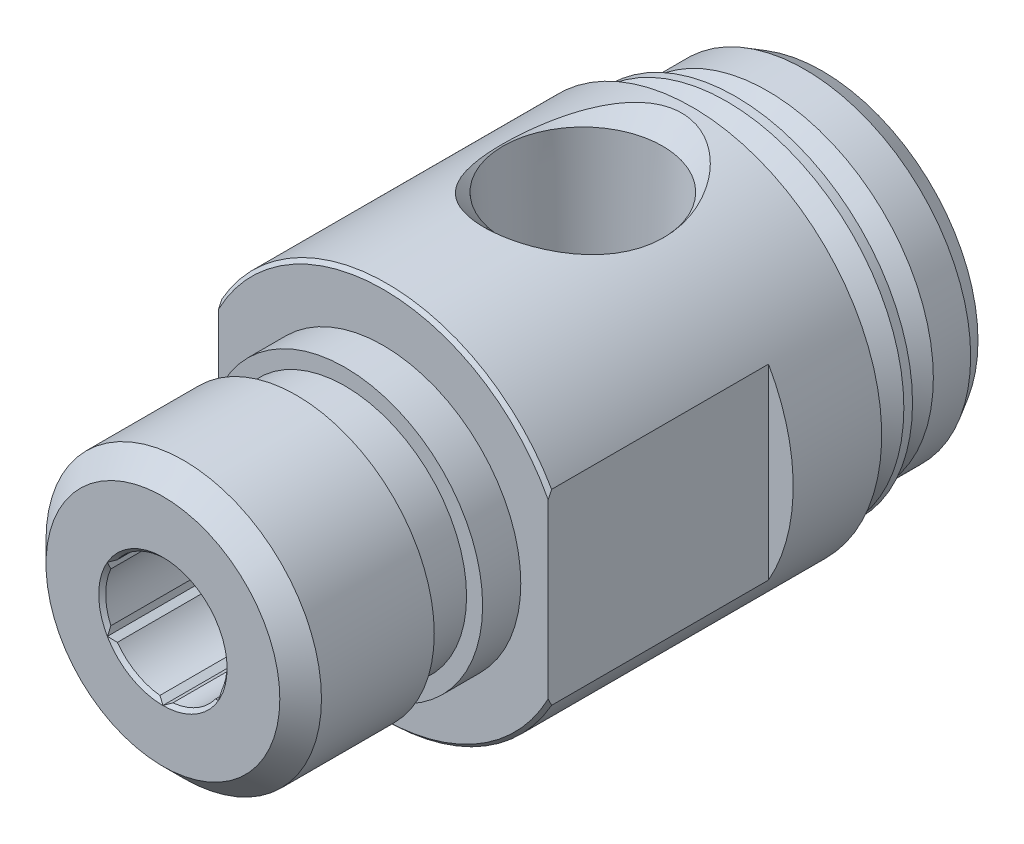
SolidWorks part; units mm, degrees
note: '?' marks a value the reader was unsure of.
ref_plane "Plane1" through (0, 0, 0) normal (0, 0, 1) x (1, 0, 0)
ref_plane "Plane2" through (0, 0, 0) normal (0, 1, 0) x (1, 0, 0)
ref_plane "Plane3" through (0, 0, 0) normal (1, 0, 0) x (0, 0, -1)
sketch "Sketch1" plane through (0, 0, 0) normal (0, 0, 1) x (1, 0, 0)
  circle A0 centre (0, 0) radius 9.55
  dimension "D1" = 19.1
extrude "TubeInterface1" add sketch "Sketch1" along normal blind 5
sketch "Sketch3" plane through (0, 0, 5) normal (0, 0, 1) x (1, 0, 0)
  circle A0 centre (0, 0) radius 10.922
  dimension "D1" = 21.844
extrude "Body" add sketch "Sketch3" along normal blind 20.3
chamfer "BodyChamfer" distance 0.2 angle 45 1 edges at (10.922, 0, 25.3)
sketch "Sketch4" plane through (0, 0, 25.3) normal (0, 0, 1) x (1, 0, 0)
  line L0 (0, 0) -> (0, 17.3061) construction
  line L1 (-9.5, 37.5) -> (-9.5, -37.5)
  line L2 (0, 0) -> (26.7246, 0) construction
  line L3 (9.5, 37.5) -> (9.5, -37.5)
  line L4 (9.5, 37.5) -> (19.5, 37.5)
  line L5 (19.5, 37.5) -> (19.5, -37.5)
  line L6 (-9.5, 37.5) -> (-19.5, 37.5)
  line L7 (-19.5, 37.5) -> (-19.5, -37.5)
  line L8 (-9.5, -37.5) -> (-19.5, -37.5)
  line L9 (9.5, -37.5) -> (19.5, -37.5)
  dimension "D1" = 19
  dimension "D2" = 10
  dimension "D3" = 75
extrude "Flats" cut sketch "Sketch4" against normal blind 12.7
sketch "Sketch5" plane through (0, 0, 25.3) normal (0, 0, 1) x (1, 0, 0)
  circle A0 centre (0, 0) radius 7.9375
  dimension "NN" = 15.875
extrude "MountThread1" add sketch "Sketch5" along normal blind 12.7
chamfer "MountThreadChamfer" distance 1.2 angle 45 1 edges at (7.9375, 0, 38)
sketch "Sketch17" plane through (0, 0, 0) normal (1, 0, 0) x (0, 0, -1)
  line L0 (-27.5, 17.727) -> (-27.5, -12.2127) construction
  line L1 (-25.3, -4.971) -> (-25.3, -10.722) construction
  line L2 (0, 0) -> (-12.6638, 0) construction
  line L3 (-25.1, 0) -> (-25.3, 0) construction
  line L6 (-30.3, 12) -> (-27.5, 12)
  line L7 (-30.3, 12) -> (-30.3, 7)
  line L8 (-30.3, 7) -> (-27.5, 7)
  line L9 (-27.5, 12) -> (-27.5, 7)
  dimension "D1" = 2.8
  dimension "D2" = 2.2
  dimension "D3" = 7
  dimension "D4" = 5
revolve "Cut-Revolve1" cut sketch "Sketch17" angle 360 about L2
sketch "Sketch8" plane through (0, 0, 0) normal (0, 0, 1) x (1, 0, 0)
  circle A0 centre (0, 0) radius 3.5
  dimension "D1" = 7
extrude "ThruBore" cut sketch "Sketch8" along normal through all
sketch "Sketch21" plane through (0, 0, 38) normal (0, 0, 1) x (1, 0, 0)
  line L0 (9.5, 4.971) -> (9.5, -4.971) construction
  line L1 (3.2, -1.8475) -> (3.2, 1.8475)
  line L2 (3.2, 1.8475) -> (0, 3.695)
  line L3 (0, 3.695) -> (-3.2, 1.8475)
  line L4 (-3.2, 1.8475) -> (-3.2, -1.8475)
  line L5 (-3.2, -1.8475) -> (0, -3.695)
  line L6 (0, -3.695) -> (3.2, -1.8475)
  circle A0 centre (0, 0) radius 3.2 construction
  dimension "D1" = 6.4
extrude "ThruBore2" cut sketch "Sketch21" against normal up to surface (38 mm away) up to face at (3.5, 0, 0)
sketch "Sketch25" plane through (0, 0, 0) normal (1, 0, 0) x (0, 0, -1)
  line L0 (-23.9202, 0) -> (-17.0101, 0) construction
  line L1 (-38, 0) -> (0, 0) construction
  line L2 (-38, 3.7) -> (-36, 1.7)
  line L3 (-38, 6.7375) -> (-38, -6.7375) construction
  line L4 (-38, -3.7) -> (-36, -1.7)
  line L5 (-36, 1.7) -> (-38, 1.7)
  line L6 (-36, -1.7) -> (-38, -1.7)
  line L7 (-38, 1.7) -> (-38, 3.7)
  line L8 (-38, -1.7) -> (-38, -3.7)
  dimension "D1" = 45
  dimension "D2" = 7.4
  dimension "D3" = 2
revolve "Chamfer1" cut sketch "Sketch25" angle 360 about L0
ref_plane "PortPlane" through (0, 10.922, 15.05) normal (0, 1, 0) x (1, 0, 0)
sketch "Sketch16" plane through (0, 10.922, 15.05) normal (0, 1, 0) x (1, 0, 0)
  line L0 (9.55, 15.05) -> (-9.55, 15.05) construction
  circle A0 centre (0, 1.25) radius 4.639
  dimension "D2" = 9.278
  dimension "D1" = 13.8
extrude "Port2" cut sketch "Sketch16" against normal up to surface (10.922 mm away) draft 2
ref_axis "Axis1" through (0, 60.922, 13.8) along (0, -1, 0)?
sketch "Sketch22" plane through (0, 0, 0) normal (1, 0, 0) x (0, 0, -1)
  line L0 (-18.439, 10.922) -> (-25.1, 10.922) construction
  line L1 (-15.8, 10.922) -> (-19.5, 10.922)
  line L2 (-19.5, 10.922) -> (-15.8, 7.222)
  line L3 (-15.8, 7.222) -> (-15.8, 10.922)
  line L5 (-13.8, 60.922) -> (-13.8, -189.078) construction
  line L6 (-13.8, 0) -> (-13.8, -3.9744) construction
  dimension "D1" = 45
  dimension "D2" = 5.7
  dimension "D3" = 2
revolve "PortChamfer" cut sketch "Sketch22" angle 360 about L6
sketch "Sketch23" plane through (0, 0, 0) normal (1, 0, 0) x (0, 0, -1)
  line L0 (-5, -10.922) -> (-5, 10.922) construction
  line L1 (-7.5, 13.6) -> (-5, 13.6)
  line L2 (-7.5, 13.6) -> (-7.5, 8.6)
  line L3 (-5.5, 10.2) -> (-5, 10.2)
  line L4 (-5, 13.6) -> (-5, 10.2)
  line L6 (-7.5, 8.6) -> (-7.1, 8.6)
  line L7 (-7.1, 8.6) -> (-5.5, 10.2)
  line L8 (0, 0) -> (13.4077, 0) construction
  line L9 (-40.223, 0) -> (-33.554, 0) construction
  dimension "D1" = 2.5
  dimension "D2" = 10.2
  dimension "D3" = 1.6
  dimension "D4" = 5
  dimension "D5" = 0.5
  dimension "D6" = 45
revolve "RodCoverCrimp" cut sketch "Sketch23" angle 360 about L8
sketch "Sketch24" plane through (0, 0, 0) normal (1, 0, 0) x (0, 0, -1)
  line L0 (-5, 14.7) -> (-5, 8.9)
  line L1 (0, 9.55) -> (-5, 9.55) construction
  line L2 (-4.7, 8.6) -> (-4.1, 8.6)
  line L3 (-4.1, 8.6) -> (-3.15, 9.55)
  line L5 (-3.15, 9.55) -> (-1, 9.55)
  line L6 (-1, 9.55) -> (0, 8.9726)
  line L7 (0, -9.55) -> (0, 9.55) construction
  line L8 (0, 8.9726) -> (0, 14.7)
  line L9 (0, 14.7) -> (-5, 14.7)
  line L11 (0, 0) -> (15.8541, 0) construction
  line L12 (-25.1, 0) -> (-12.6, 0) construction
  arc A0 (-5, 8.9) -> (-4.7, 8.6) centre (-4.7, 8.9) ccw
  point P21 (-5, 8.6)
  dimension "D7" = 0.3
  dimension "D1" = 0.9
  dimension "D2" = 45
  dimension "D3" = 8.6
  dimension "D4" = 60
  dimension "D5" = 1
  dimension "D6" = 5.8
  dimension "D8" = 5
revolve "TubeInterfaceCrimp" cut sketch "Sketch24" angle 360 about L11
sketch "Sketch26" plane through (0, 0, 0) normal (1, 0, 0) x (0, 0, -1)
  line L0 (-25.3, 7.9375) -> (-27.5, 7.9375)
  line L1 (-27.5, 7.9375) -> (-27.5, 7.9248)
  line L2 (-27.5, 7.9375) -> (-27.5, -7.9375) construction
  line L3 (-27.5, 7.9248) -> (-25.3, 7.9248)
  line L4 (-25.3, 7.9375) -> (-25.3, -7.9375) construction
  line L5 (-25.3, 7.9248) -> (-25.3, 7.9375)
  line L6 (-38, 0) -> (-41.6305, 0) construction
  line L7 (-38, 6.7375) -> (-38, -6.7375) construction
  dimension "B" = 15.8496
revolve "Cut-Revolve2" cut sketch "Sketch26" angle 360 about L6
ref_plane "Speed Controller mate plane" through (0, 10.922, 0) normal (0, 1, 0) x (-1, 0, 0)
